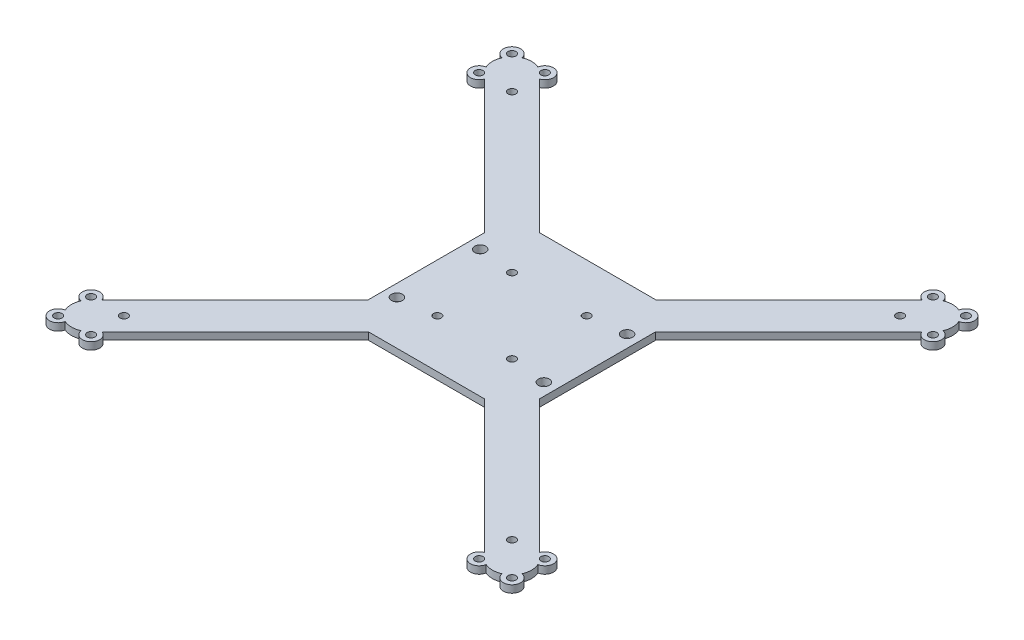
SolidWorks part; units mm, degrees
ref_plane "Front Plane" through (0, 0, 0) normal (0, 0, 1) x (1, 0, 0)
ref_plane "Top Plane" through (0, 0, 0) normal (0, 1, 0) x (1, 0, 0)
ref_plane "Right Plane" through (0, 0, 0) normal (1, 0, 0) x (0, 0, -1)
sketch "Sketch1" plane through (0, 0, 0) normal (0, 1, 0) x (1, 0, 0)
  line L1 (-23.6863, -35) -> (23.6863, -35)
  line L2 (-35, -23.6863) -> (-35, 23.6863)
  line L3 (-23.6863, 35) -> (23.6863, 35)
  line L4 (35, -23.6863) -> (35, 23.6863)
  line L5 (-35, -35) -> (42.6186, 42.6186) construction
  line L6 (-35, 35) -> (35, -35) construction
  line L7 (35, 23.6863) -> (89.3815, 78.0678)
  line L8 (23.6863, 35) -> (78.0678, 89.3815)
  line L9 (0, 0) -> (54.3815, 54.3815) construction
  line L10 (79.2432, 92.6782) -> (92.6782, 79.2432) construction
  line L11 (30, 17) -> (30, 0) construction
  line L12 (0, 0) -> (0, 23.6863) construction
  line L13 (35, -23.6863) -> (89.3815, -78.0678)
  line L14 (23.6863, -35) -> (78.0678, -89.3815)
  line L15 (-23.6863, -35) -> (-78.0678, -89.3815)
  line L16 (-35, -23.6863) -> (-89.3815, -78.0678)
  line L17 (-35, 23.6863) -> (-89.3815, 78.0678)
  line L18 (-23.6863, 35) -> (-78.0678, 89.3815)
  circle A0 centre (-15.25, 15.25) radius 1.6
  circle A1 centre (15.25, 15.25) radius 1.6
  circle A2 centre (15.25, -15.25) radius 1.6
  circle A3 centre (-15.25, -15.25) radius 1.6
  arc A5 (93.2633, 89.2274) -> (89.2274, 93.2633) centre (92.6782, 92.6782) ccw
  arc A9 (93.8536, 82.5399) -> (93.2633, 82.6939) centre (92.6782, 79.2432) ccw
  arc A10 (89.2274, 93.2633) -> (82.6939, 93.2633) centre (85.9607, 85.9607) ccw
  circle A11 centre (92.6782, 92.6782) radius 1.6
  circle A12 centre (92.6782, 79.2432) radius 1.6
  circle A13 centre (79.2432, 79.2432) radius 1.6
  circle A14 centre (79.2432, 92.6782) radius 1.6
  arc A15 (93.2633, 82.6939) -> (93.2633, 89.2274) centre (85.9607, 85.9607) ccw
  arc A16 (82.6939, 93.2633) -> (82.5399, 93.8536) centre (79.2432, 92.6782) ccw
  arc A17 (78.6581, 82.6939) -> (76.7683, 76.7683) centre (79.2432, 79.2432) ccw [skipped]
  circle A18 centre (30, 17) radius 2.25
  circle A19 centre (30, -17) radius 2.25
  circle A20 centre (-30, -17) radius 2.25
  circle A21 centre (-30, 17) radius 2.25
  arc A22 (78.0678, 89.3815) -> (82.5399, 93.8536) centre (79.2432, 92.6782) cw
  arc A23 (93.2633, -89.2274) -> (93.2633, -82.6939) centre (85.9607, -85.9607) ccw
  circle A24 centre (92.6782, 92.6782) radius 1.6
  circle A25 centre (79.2432, 79.2432) radius 1.6
  arc A26 (82.6939, -93.2633) -> (89.2274, -93.2633) centre (85.9607, -85.9607) ccw
  arc A27 (93.8536, 82.5399) -> (89.3815, 78.0678) centre (92.6782, 79.2432) cw
  arc A28 (78.0678, -89.3815) -> (82.6939, -93.2633) centre (79.2432, -92.6782) ccw
  circle A29 centre (79.2432, -92.6782) radius 1.6
  circle A30 centre (79.2432, -79.2432) radius 1.6
  circle A31 centre (92.6782, -79.2432) radius 1.6
  arc A32 (93.2633, -82.6939) -> (89.3815, -78.0678) centre (92.6782, -79.2432) ccw
  arc A33 (89.2274, -93.2633) -> (93.2633, -89.2274) centre (92.6782, -92.6782) ccw
  circle A34 centre (92.6782, -92.6782) radius 1.6
  arc A35 (-89.2274, -93.2633) -> (-82.6939, -93.2633) centre (-85.9607, -85.9607) ccw
  arc A36 (-93.2633, -82.6939) -> (-93.2633, -89.2274) centre (-85.9607, -85.9607) ccw
  arc A37 (-89.3815, -78.0678) -> (-93.2633, -82.6939) centre (-92.6782, -79.2432) ccw
  circle A38 centre (-92.6782, -79.2432) radius 1.6
  circle A39 centre (-79.2432, -79.2432) radius 1.6
  circle A40 centre (-79.2432, -92.6782) radius 1.6
  arc A41 (-82.6939, -93.2633) -> (-78.0678, -89.3815) centre (-79.2432, -92.6782) ccw
  arc A42 (-93.2633, -89.2274) -> (-89.2274, -93.2633) centre (-92.6782, -92.6782) ccw
  circle A43 centre (-92.6782, -92.6782) radius 1.6
  arc A44 (-93.2633, 89.2274) -> (-93.2633, 82.6939) centre (-85.9607, 85.9607) ccw
  arc A45 (-82.6939, 93.2633) -> (-89.2274, 93.2633) centre (-85.9607, 85.9607) ccw
  arc A46 (-78.0678, 89.3815) -> (-82.6939, 93.2633) centre (-79.2432, 92.6782) ccw
  circle A47 centre (-79.2432, 92.6782) radius 1.6
  circle A48 centre (-79.2432, 79.2432) radius 1.6
  circle A49 centre (-92.6782, 79.2432) radius 1.6
  arc A50 (-93.2633, 82.6939) -> (-89.3815, 78.0678) centre (-92.6782, 79.2432) ccw
  arc A51 (-89.2274, 93.2633) -> (-93.2633, 89.2274) centre (-92.6782, 92.6782) ccw
  circle A52 centre (-92.6782, 92.6782) radius 1.6
  point P0 (0, 0)
  point P17 (0, 0)
  point P33 (85.9607, 85.9607)
  point P42 (85.9607, 85.9607)
  point P45 (85.9607, 85.9607)
  point P47 (30, 0)
  point P118 (0, 0)
  dimension "D3" = 3.2
  dimension "D9" = 4
  dimension "D11" = 7
  dimension "D13" = 3.2
  dimension "D16" = 4.5
  dimension "D1" = 70
  dimension "D2" = 70
  dimension "D4" = 30.5
  dimension "D6" = 16
  dimension "D8" = 100
  dimension "D10" = 9.5
  dimension "D15" = 17
  dimension "D12" = 30
  dimension "D5" = 4
  dimension "D14" = 4
  dimension "D17" = 2
  dimension "D18" = 4
extrude "Boss-Extrude1" add sketch "Sketch1" along normal blind 3 contours A45 A51 A44 A50 L17 L2 L16 A37 A36 A42 A35 A41 L15 L1 L14 A28 A26 A33 A23 A32 L13 L4 L7 A27 A9 A15 A5 A10 A16 A22 L8 L3 L18 A46 A52 A21 A0 A1 A2 A3 A11 A12 region at (0, 0, 0)
sketch "Sketch4" plane through (0, 0, 0) normal (0, -1, 0) x (1, 0, 0)
  circle A0 centre (0, 0) radius 4.9
  circle A1 centre (0, 0) radius 6.495
  dimension "D1" = 9.8
extrude "Boss-Extrude3" add sketch "Sketch4" along normal blind 5
sketch "Sketch6" plane through (0, 0, 35) normal (0, 0, 1) x (1, 0, 0)
  line L0 (-6.495, 0) -> (6.495, 0) construction
  line L1 (-4.2416, -1.8916) -> (4.2416, -1.8916)
  line L2 (-4.2416, -1.8916) -> (-4.2416, 0)
  line L3 (-4.2416, 0) -> (4.2416, 0)
  line L4 (4.2416, -1.8916) -> (4.2416, 0)
  line L5 (-4.2416, -1.8916) -> (4.2416, 0) construction
  line L6 (-4.2416, 0) -> (4.2416, -1.8916) construction
  point P0 (0, -0.9458)
  point P7 (0, 0)
  point P9 (4.2416, -1.8916)
extrude "Cut-Extrude3" cut sketch "Sketch6" against normal blind 34
